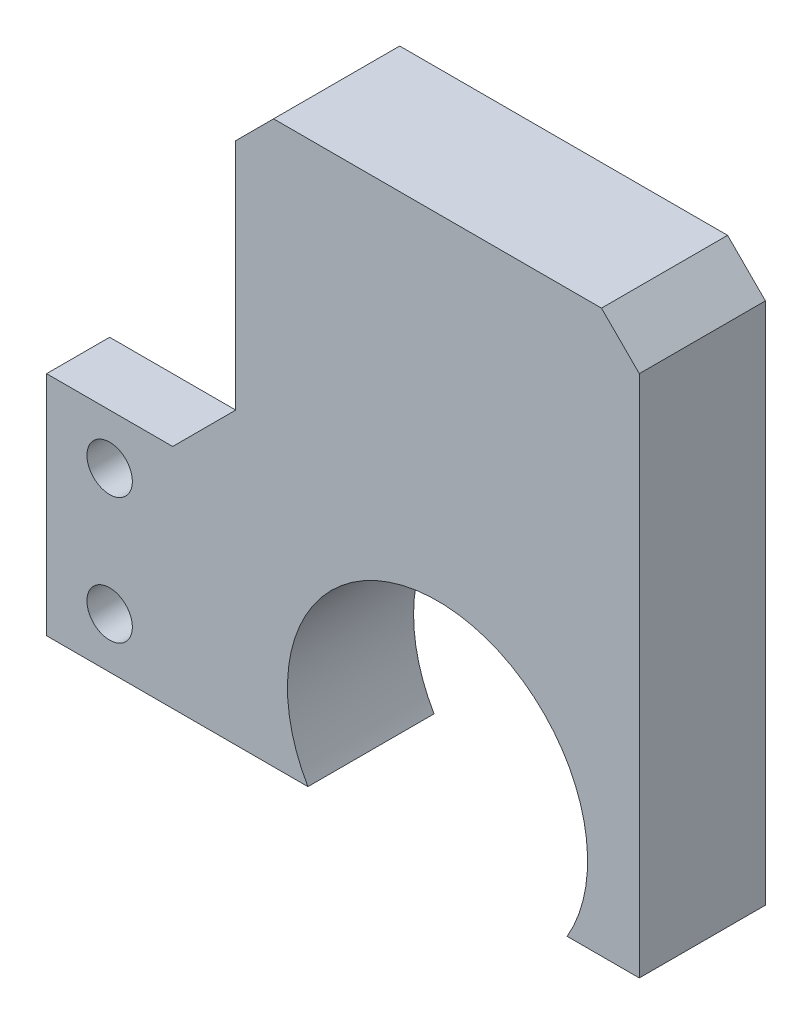
SolidWorks part; units mm, degrees
ref_plane "Płaszczyzna przednia" through (0, 0, 0) normal (0, 0, 1) x (1, 0, 0)
ref_plane "Płaszczyzna górna" through (0, 0, 0) normal (0, 1, 0) x (1, 0, 0)
ref_plane "Płaszczyzna prawa" through (0, 0, 0) normal (1, 0, 0) x (0, 0, -1)
sketch "Szkic1" plane through (0, 0, 0) normal (0, 0, 1) x (1, 0, 0)
  line L1 (-16, -22.25) -> (16, -22.25)
  line L2 (-16, -22.25) -> (-16, 22.25)
  line L3 (-16, 22.25) -> (16, 22.25)
  line L4 (16, -22.25) -> (16, 22.25)
  line L5 (0, 22.25) -> (0, -22.25) construction
  line L6 (-16, 0) -> (16, 0) construction
  point P0 (0, 0)
  dimension "D1" = 44.5
  dimension "D2" = 32
extrude "Dodanie-wyciągnięcie1" add sketch "Szkic1" along normal blind 10
sketch "Szkic2" plane through (0, 0, 10) normal (0, 0, 1) x (1, 0, 0)
  arc A4 (4.4383, -5.641) -> (4.1277, -26.9837) centre (0, -16.25) ccw construction
  arc A5 (4.4383, -5.641) -> (4.1277, -26.9837) centre (0, -16.25) ccw construction
  circle A6 centre (0, -16.25) radius 11.9
  dimension "D1" = 0.4
extrude "Wytnij-wyciągnięcie1" cut sketch "Szkic2" against normal up to next
sketch "Szkic3" plane through (0, 0, 0) normal (0, 0, 1) x (1, 0, 0)
  line L5 (8.58, 16.05) -> (-8.58, 16.05)
  line L6 (-9.8, 14.8946) -> (-9.8, -7.3)
  line L7 (-9.8, -7.3) -> (-7.1414, -7.3)
  line L8 (7.1414, -7.3) -> (9.8, -7.3)
  line L9 (9.8, -7.3) -> (9.8, 14.8946)
  line L10 (8.58, 16.05) -> (-8.58, 16.05) construction
  line L11 (-9.8, 14.8946) -> (-9.8, -7.3) construction
  line L12 (-9.8, -7.3) -> (-7.1414, -7.3) construction
  line L13 (7.1414, -7.3) -> (9.8, -7.3) construction
  line L14 (9.8, -7.3) -> (9.8, 14.8946) construction
  line L119 (10.2, -7.3) -> (10.2, 15.213)
  line L120 (8.8793, 16.45) -> (-8.8793, 16.45)
  line L121 (-10.2, 15.213) -> (-10.2, -7.3)
  line L122 (-10.2, -7.3) -> (10.2, -7.3) construction
  line L123 (-10.2, -7.3) -> (-10.2, -10.1206)
  line L124 (-10.2, -10.1206) -> (10.2, -10.1206)
  line L125 (10.2, -10.1206) -> (10.2, -7.3)
  arc A3 (-9.8, 14.8946) -> (-8.58, 16.05) centre (-10.4, 16.75) ccw
  arc A4 (7.1414, -7.3) -> (-7.1414, -7.3) centre (0, -16.25) ccw
  arc A5 (8.58, 16.05) -> (9.8, 14.8946) centre (10.4, 16.75) ccw
  arc A6 (-9.8, 14.8946) -> (-8.58, 16.05) centre (-10.4, 16.75) ccw construction
  arc A7 (7.1414, -7.3) -> (-7.1414, -7.3) centre (0, -16.25) ccw construction
  arc A8 (8.58, 16.05) -> (9.8, 14.8946) centre (10.4, 16.75) ccw construction
  arc A14 (8.8793, 16.45) -> (10.2, 15.213) centre (10.4, 16.75) ccw
  arc A15 (-10.2, 15.213) -> (-8.8793, 16.45) centre (-10.4, 16.75) ccw
  arc A16 (10.2767, -22.25) -> (-10.2767, -22.25) centre (0, -16.25) ccw construction
  dimension "D1" = 0
  dimension "D2" = 0.4
extrude "Wytnij-wyciągnięcie2" cut sketch "Szkic3" along normal blind 3.4
sketch "Szkic5" plane through (0, 0, 0) normal (0, 0, -1) x (-1, 0, 0)
  point P0 (8, 19.75)
  point P1 (13.5, 14.5)
  point P3 (13.5, 6.5)
  point P5 (13.5, -1.5)
  point P7 (13.5, -9.5)
  point P9 (-13.5, -9.5)
  point P11 (-13.5, -1.5)
  point P13 (-13.5, 6.5)
  point P15 (-13.5, 14.5)
  point P17 (-8, 19.75)
hole_wizard "Otwór Ø3.2 (3.2)1" positions "Szkic5" profile "Szkic6" hole size "Ø3.2" standard "DIN"
sketch "Szkic6" plane through (-8, 19.75, 0) normal (1, 0, 0) x (0, 1, 0)
  line L0 (0, 0) -> (0, 4)
  line L1 (0, 4) -> (1.6, 4)
  line L2 (1.6, 4) -> (1.6, 0)
  line L5 (1.6, 0) -> (0, 0)
  line L10 (0, 4) -> (-1.6, 4) construction
  line L11 (0, -6.35) -> (0, 107.95) construction
  dimension "Średnica otworu" = 3.2
  dimension "Głębokość otworu" = 4
  dimension "Kąt wiertła" = 180
sketch "Szkic7" plane through (0, 0, 10) normal (0, 0, 1) x (1, 0, 0)
  line L1 (-16, -22.25) -> (-31, -22.25)
  line L2 (-16, -22.25) -> (-16, -4.25)
  line L3 (-16, -4.25) -> (-31, -4.25)
  line L4 (-31, -22.25) -> (-31, -4.25)
  line L5 (-23.5, -4.25) -> (-23.5, -22.25) construction
  line L6 (-16, -13.25) -> (-31, -13.25) construction
  point P212 (-23.5, -13.25)
  dimension "D1" = 18
  dimension "D2" = 15
extrude "Dodanie-wyciągnięcie2" add sketch "Szkic7" against normal blind 5
chamfer "Sfazowanie1" distance 5 angle 45 2 edges at (-16, -13.25, 5) (-16, -4.25, 7.5)
chamfer "Sfazowanie2" distance 3 angle 45 2 edges at (16, 22.25, 5) (-16, 22.25, 5)
sketch "Szkic8" plane through (0, 0, 5) normal (0, 0, -1) x (-1, 0, 0)
  line L0 (26, -4.25) -> (26, -22.25) construction
  line L1 (21, -4.25) -> (31, -4.25) construction
  line L2 (31, -22.25) -> (21, -22.25) construction
  line L3 (21, -13.25) -> (31, -13.25) construction
  line L4 (21, -4.25) -> (21, -22.25) construction
  line L5 (31, -4.25) -> (31, -22.25) construction
  point P6 (26, -8.25)
  point P7 (26, -18.25)
  point P14 (0, 0)
  dimension "D1" = 5
hole_wizard "Pogłębienie walcowe pod M3 Śrubę z łbem stożkowym ściętym1" positions "Szkic8" profile "Szkic9" counterbore size "M3" standard "DIN"
sketch "Szkic9" plane through (-26, -18.25, 5) normal (1, 0, 0) x (0, 1, 0)
  line L0 (0, 0) -> (0, 25.0815)
  line L1 (0, 25.0815) -> (1.8, 24)
  line L2 (1.8, 24) -> (1.8, 2.4)
  line L3 (1.8, 2.4) -> (3.5, 2.4)
  line L4 (3.5, 2.4) -> (3.5, 0)
  line L5 (3.5, 0) -> (0, 0)
  line L10 (0, 25.0815) -> (-1.8, 24) construction
  line L11 (0, -6.35) -> (0, 107.95) construction
  dimension "Średnica otworu" = 3.6
  dimension "Głębokość otworu" = 24
  dimension "Średnica pogłębienia walcowego" = 7
  dimension "Głębokość pogłębienia walcowego" = 2.4
  dimension "Kąt wiertła" = 118
